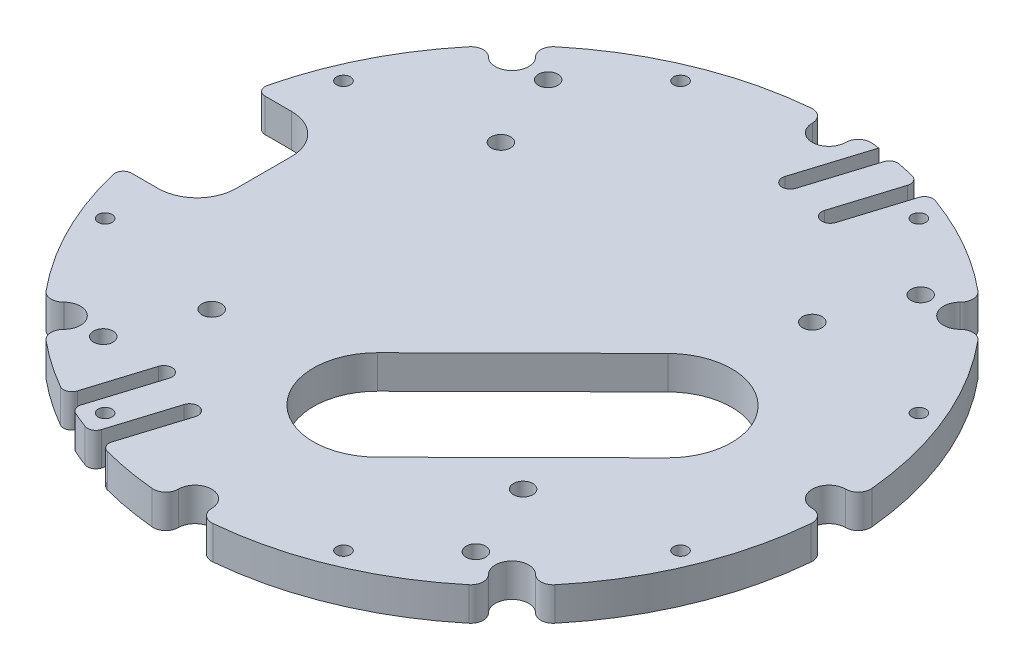
SolidWorks part; units mm, degrees
ref_plane "Ebene vorne" through (0, 0, 0) normal (0, 0, 1) x (1, 0, 0)
ref_plane "Ebene oben" through (0, 0, 0) normal (0, 1, 0) x (1, 0, 0)
ref_plane "Ebene rechts" through (0, 0, 0) normal (1, 0, 0) x (0, 0, -1)
sketch "Skizze1" plane through (0, 90.4001, 0) normal (0, 1, 0) x (1, 0, 0)
  line L0 (53.911, -33.2829) -> (49.3933, -47.7835)
  line L1 (24.4168, -148.1218) -> (28.8822, -133.7891)
  line L3 (-14.1957, -79.9654) -> (-7.542, -79.9654)
  line L4 (-0.542, -86.9654) -> (-0.542, -96.9654)
  line L5 (-7.542, -103.9654) -> (-14.1957, -103.9654)
  line L6 (-14.7061, -103.9654) -> (-7.542, -103.9654) construction
  line L7 (50.937, -32.8616) -> (46.3688, -47.5242)
  line L8 (10.5816, -51.9654) -> (77.5816, -131.9654) construction
  line L9 (27.3063, -149.0516) -> (31.7689, -134.728)
  line L10 (58.236, -49.7765) -> (62.6986, -35.4529)
  line L11 (77.5816, -51.9654) -> (10.5816, -51.9654) construction
  line L12 (23.359, -131.3458) -> (18.8412, -145.8464)
  line L13 (77.5816, -51.9654) -> (77.5816, -131.9654) construction
  line L14 (55.3269, -48.9096) -> (59.7923, -34.577)
  line L15 (77.5816, -131.9654) -> (10.5816, -131.9654) construction
  line L16 (20.7224, -129.8414) -> (16.1542, -144.504)
  line L18 (10.5816, -51.9654) -> (10.5816, -131.9654) construction
  line L19 (16.0816, -65.9654) -> (72.0816, -117.9654) construction
  line L20 (16.0816, -65.9654) -> (72.0816, -65.9654) construction
  line L21 (16.0816, -65.9654) -> (16.0816, -117.9654) construction
  line L22 (16.0816, -117.9654) -> (72.0816, -117.9654) construction
  line L23 (72.0816, -65.9654) -> (72.0816, -117.9654) construction
  line L24 (55.3269, -48.9096) -> (28.8822, -133.7891) construction
  line L27 (63.9849, -83.7988) -> (37.7607, -109.7988)
  line L28 (25.5156, -144.595) -> (19.7872, -142.8103) construction
  line L29 (80.1784, -100.1319) -> (53.9541, -126.1319)
  arc A0 (-5.9729, -58.8814) -> (-14.7061, -79.9654) centre (44.0816, -91.9654) ccw construction
  arc A1 (-5.9729, -58.8814) -> (-14.7061, -79.9654) centre (44.0816, -91.9654) ccw construction
  circle A2 centre (44.0816, -91.9654) radius 59.5
  arc A5 (-7.542, -79.9654) -> (-7.542, -103.9654) centre (44.0816, -91.9654) ccw construction
  arc A6 (-7.542, -79.9654) -> (-7.542, -103.9654) centre (44.0816, -91.9654) ccw construction
  arc A7 (-7.542, -79.9654) -> (-0.542, -86.9654) centre (-7.542, -86.9654) cw
  arc A8 (-0.542, -96.9654) -> (-7.542, -103.9654) centre (-7.542, -96.9654) cw
  circle A9 centre (22.6514, -40.2281) radius 1.25 construction
  circle A10 centre (22.6514, -40.2281) radius 1.25
  circle A11 centre (-7.6556, -70.5351) radius 1.25 construction
  circle A12 centre (-7.6556, -113.3956) radius 1.25 construction
  circle A13 centre (22.6514, -143.7026) radius 1.25 construction
  circle A14 centre (65.5119, -143.7026) radius 1.25 construction
  circle A15 centre (95.8189, -113.3956) radius 1.25 construction
  circle A16 centre (95.8189, -70.5351) radius 1.25 construction
  circle A17 centre (65.5119, -40.2281) radius 1.25 construction
  circle A18 centre (-7.6556, -70.5351) radius 1.25
  circle A19 centre (-7.6556, -113.3956) radius 1.25
  circle A20 centre (22.6514, -143.7026) radius 1.25
  circle A21 centre (65.5119, -143.7026) radius 1.25
  circle A22 centre (95.8189, -113.3956) radius 1.25
  circle A23 centre (95.8189, -70.5351) radius 1.25
  circle A24 centre (65.5119, -40.2281) radius 1.25
  arc A26 (49.3933, -47.7835) -> (46.3688, -47.5242) centre (44.0816, -91.9654) ccw
  arc A28 (55.3269, -48.9096) -> (49.3933, -47.7835) centre (44.0816, -91.9654) ccw construction
  arc A29 (31.7689, -134.728) -> (58.236, -49.7765) centre (44.0816, -91.9654) ccw construction
  arc A30 (58.236, -49.7765) -> (55.3269, -48.9096) centre (44.0816, -91.9654) ccw
  arc A31 (46.3688, -47.5242) -> (20.7224, -129.8414) centre (44.0816, -91.9654) ccw construction
  arc A32 (20.7224, -129.8414) -> (23.359, -131.3458) centre (44.0816, -91.9654) ccw
  arc A33 (23.359, -131.3458) -> (28.8822, -133.7891) centre (44.0816, -91.9654) ccw construction
  arc A34 (28.8822, -133.7891) -> (31.7689, -134.728) centre (44.0816, -91.9654) ccw
  circle A35 centre (77.5816, -51.9654) radius 1.75
  circle A36 centre (10.5816, -51.9654) radius 1.75
  circle A37 centre (10.5816, -131.9654) radius 1.75
  circle A38 centre (77.5816, -131.9654) radius 1.75
  circle A39 centre (16.0816, -65.9654) radius 1.75
  circle A40 centre (72.0816, -65.9654) radius 1.75
  circle A41 centre (72.0816, -117.9654) radius 1.75
  circle A42 centre (16.0816, -117.9654) radius 1.75
  arc A46 (80.1784, -100.1319) -> (63.9849, -83.7988) centre (72.0816, -91.9654) ccw
  arc A47 (37.7607, -109.7988) -> (53.9541, -126.1319) centre (45.8574, -117.9654) ccw
  point P5 (59.8996, -34.6182)
  point P17 (50.1571, -32.9645)
  point P18 (47.4097, -47.4938)
  point P78 (52.7585, -33.1014)
  point P83 (53.74, -33.2545)
  point P84 (17.0241, -144.9572)
  point P85 (0, 0)
  point P86 (15.4276, -144.3002)
  point P87 (50.8337, -32.5842)
  point P88 (53.9541, -33.2829)
  dimension "D1" = 119
  dimension "D2" = 6
  dimension "D3" = 12
  dimension "D4" = 89
  dimension "D6" = 3.5
  dimension "D11" = 23
  dimension "D5" = 10
  dimension "D7" = 67
  dimension "D8" = 80
  dimension "D9" = 56
  dimension "D10" = 52
extrude "Aufsatz-Linear austragen1" add sketch "Skizze1" along normal blind 6
sketch "Skizze2" plane through (0, 90.4001, 0) normal (0, 1, 0) x (1, 0, 0)
  line L11 (-7.542, -103.9654) -> (-14.1957, -103.9654)
  line L12 (16.1542, -144.504) -> (20.7224, -129.8414)
  line L13 (23.359, -131.3458) -> (18.8412, -145.8464)
  line L14 (24.4168, -148.1218) -> (28.8822, -133.7891)
  line L15 (31.7689, -134.728) -> (27.3063, -149.0516)
  line L16 (62.6986, -35.4529) -> (58.236, -49.7765)
  line L17 (55.3269, -48.9096) -> (59.7923, -34.577)
  line L18 (53.911, -33.2829) -> (49.3933, -47.7835)
  line L19 (46.3688, -47.5242) -> (50.937, -32.8616)
  line L20 (-14.1957, -79.9654) -> (-7.542, -79.9654)
  line L21 (-0.542, -86.9654) -> (-0.542, -96.9654)
  line L22 (-7.542, -103.9654) -> (-14.1957, -103.9654)
  line L23 (16.1542, -144.504) -> (20.7224, -129.8414)
  line L24 (23.359, -131.3458) -> (18.8412, -145.8464)
  line L25 (24.4168, -148.1218) -> (28.8822, -133.7891)
  line L26 (31.7689, -134.728) -> (27.3063, -149.0516)
  line L27 (62.6986, -35.4529) -> (58.236, -49.7765)
  line L28 (55.3269, -48.9096) -> (59.7923, -34.577)
  line L29 (53.911, -33.2829) -> (49.3933, -47.7835)
  line L30 (46.3688, -47.5242) -> (50.937, -32.8616)
  line L31 (-14.1957, -79.9654) -> (-7.542, -79.9654)
  line L32 (-0.542, -86.9654) -> (-0.542, -96.9654)
  circle A0 centre (44.0816, -91.9654) radius 43
  circle A1 centre (44.0816, -91.9654) radius 45
  arc A11 (-7.542, -103.9654) -> (-0.542, -96.9654) centre (-7.542, -96.9654) ccw
  arc A12 (-14.1957, -103.9654) -> (16.1542, -144.504) centre (44.0816, -91.9654) ccw
  arc A13 (20.7224, -129.8414) -> (23.359, -131.3458) centre (44.0816, -91.9654) ccw
  arc A14 (18.8412, -145.8464) -> (24.4168, -148.1218) centre (44.0816, -91.9654) ccw
  arc A15 (28.8822, -133.7891) -> (31.7689, -134.728) centre (44.0816, -91.9654) ccw
  arc A16 (27.3063, -149.0516) -> (62.6986, -35.4529) centre (44.0816, -91.9654) ccw
  arc A17 (58.236, -49.7765) -> (55.3269, -48.9096) centre (44.0816, -91.9654) ccw
  arc A18 (59.7923, -34.577) -> (53.911, -33.2829) centre (44.0816, -91.9654) ccw
  arc A19 (49.3933, -47.7835) -> (46.3688, -47.5242) centre (44.0816, -91.9654) ccw
  arc A20 (50.937, -32.8616) -> (-14.1957, -79.9654) centre (44.0816, -91.9654) ccw
  arc A21 (-0.542, -86.9654) -> (-7.542, -79.9654) centre (-7.542, -86.9654) ccw
  arc A22 (-7.542, -103.9654) -> (-0.542, -96.9654) centre (-7.542, -96.9654) ccw
  arc A23 (-14.1957, -103.9654) -> (16.1542, -144.504) centre (44.0816, -91.9654) ccw
  arc A24 (20.7224, -129.8414) -> (23.359, -131.3458) centre (44.0816, -91.9654) ccw
  arc A25 (18.8412, -145.8464) -> (24.4168, -148.1218) centre (44.0816, -91.9654) ccw
  arc A26 (28.8822, -133.7891) -> (31.7689, -134.728) centre (44.0816, -91.9654) ccw
  arc A27 (27.3063, -149.0516) -> (62.6986, -35.4529) centre (44.0816, -91.9654) ccw
  arc A28 (58.236, -49.7765) -> (55.3269, -48.9096) centre (44.0816, -91.9654) ccw
  arc A29 (59.7923, -34.577) -> (53.911, -33.2829) centre (44.0816, -91.9654) ccw
  arc A30 (49.3933, -47.7835) -> (46.3688, -47.5242) centre (44.0816, -91.9654) ccw
  arc A31 (50.937, -32.8616) -> (-14.1957, -79.9654) centre (44.0816, -91.9654) ccw construction
  arc A32 (-0.542, -86.9654) -> (-7.542, -79.9654) centre (-7.542, -86.9654) ccw
  dimension "D2" = 86
  dimension "D3" = 90
  dimension "D1" = 0
extrude "Schnitt-Linear austragen1" cut sketch "Skizze2" along normal blind 2 contours A1 A0
sketch "Skizze3" plane through (0, 96.4001, 0) normal (0, 1, 0) x (1, 0, 0)
  line L0 (1.6552, -53.7816) -> (5.8979, -49.539) construction
  circle A0 centre (44.0816, -34.9654) radius 1.25 construction
  circle A1 centre (84.3867, -51.6603) radius 1.25 construction
  circle A2 centre (101.0816, -91.9654) radius 1.25 construction
  circle A3 centre (84.3867, -132.2704) radius 1.25 construction
  circle A5 centre (3.7766, -132.2704) radius 1.25 construction
  circle A7 centre (3.7766, -51.6603) radius 1.25 construction
  circle A8 centre (44.0816, -34.9654) radius 1.25 construction
  circle A9 centre (84.3867, -51.6603) radius 1.25 construction
  circle A10 centre (101.0816, -91.9654) radius 1.25 construction
  circle A11 centre (84.3867, -132.2704) radius 1.25 construction
  circle A13 centre (3.7766, -132.2704) radius 1.25 construction
  circle A15 centre (3.7766, -51.6603) radius 1.25 construction
  arc A16 (50.937, -32.8616) -> (-14.1957, -79.9654) centre (44.0816, -91.9654) ccw construction
  arc A17 (6.0513, -46.2057) -> (5.8979, -49.539) centre (7.4945, -47.9423) ccw
  arc A18 (5.8979, -49.539) -> (1.6552, -53.7816) centre (3.7766, -51.6603) cw
  arc A19 (1.6552, -53.7816) -> (-1.678, -53.935) centre (0.0586, -55.3782) ccw
  circle A20 centre (44.0816, -91.9654) radius 59.5 construction
  arc A21 (49.547, -32.7169) -> (47.0816, -34.9654) centre (49.3396, -34.9654) ccw
  arc A22 (47.0816, -34.9654) -> (41.0816, -34.9654) centre (44.0816, -34.9654) cw
  arc A23 (41.0816, -34.9654) -> (38.6162, -32.7169) centre (38.8236, -34.9654) ccw
  arc A24 (89.8412, -53.935) -> (86.508, -53.7816) centre (88.1047, -55.3782) ccw
  arc A25 (86.508, -53.7816) -> (82.2654, -49.539) centre (84.3867, -51.6603) cw
  arc A26 (82.2654, -49.539) -> (82.112, -46.2057) centre (80.6688, -47.9423) ccw
  arc A27 (103.3301, -97.4308) -> (101.0816, -94.9654) centre (101.0816, -97.2234) ccw
  arc A28 (101.0816, -94.9654) -> (101.0816, -88.9654) centre (101.0816, -91.9654) cw
  arc A29 (101.0816, -88.9654) -> (103.3301, -86.5) centre (101.0816, -86.7074) ccw
  arc A30 (82.112, -137.725) -> (82.2654, -134.3918) centre (80.6688, -135.9884) ccw
  arc A31 (82.2654, -134.3918) -> (86.508, -130.1491) centre (84.3867, -132.2704) cw
  arc A32 (86.508, -130.1491) -> (89.8412, -129.9957) centre (88.1047, -128.5525) ccw
  arc A33 (38.6162, -151.2138) -> (41.0816, -148.9654) centre (38.8236, -148.9654) ccw
  arc A34 (41.0816, -148.9654) -> (47.0816, -148.9654) centre (44.0816, -148.9654) cw
  arc A35 (47.0816, -148.9654) -> (49.547, -151.2138) centre (49.3396, -148.9654) ccw
  arc A36 (-1.678, -129.9957) -> (1.6552, -130.1491) centre (0.0586, -128.5525) ccw
  arc A37 (1.6552, -130.1491) -> (5.8979, -134.3918) centre (3.7766, -132.2704) cw
  arc A38 (5.8979, -134.3918) -> (6.0513, -137.725) centre (7.4945, -135.9884) ccw
  arc A39 (-15.1668, -86.5) -> (-12.9184, -88.9654) centre (-12.9184, -86.7074) ccw construction
  arc A40 (-12.9184, -88.9654) -> (-12.9184, -94.9654) centre (-12.9184, -91.9654) cw construction
  arc A44 (-12.9184, -94.9654) -> (-15.1668, -97.4308) centre (-12.9184, -97.2234) ccw construction
  circle A45 centre (44.0816, -91.9654) radius 75
  point P82 (44.0816, -91.9654)
  arc M30 (-0.542, -96.9654) -> (-7.542, -103.9654) centre (-7.542, -96.9654) cw
  line M31 (-7.542, -103.9654) -> (-14.1957, -103.9654)
  arc M32 (-14.1957, -103.9654) -> (16.1542, -144.504) centre (44.0816, -91.9654) ccw
  line M33 (16.1542, -144.504) -> (20.7224, -129.8414)
  arc M34 (20.7224, -129.8414) -> (23.359, -131.3458) centre (44.0816, -91.9654) ccw
  line M35 (23.359, -131.3458) -> (18.8412, -145.8464)
  arc M36 (18.8412, -145.8464) -> (24.4168, -148.1218) centre (44.0816, -91.9654) ccw
  line M37 (24.4168, -148.1218) -> (28.8822, -133.7891)
  arc M38 (28.8822, -133.7891) -> (31.7689, -134.728) centre (44.0816, -91.9654) ccw
  line M39 (31.7689, -134.728) -> (27.3063, -149.0516)
  arc M40 (27.3063, -149.0516) -> (62.6986, -35.4529) centre (44.0816, -91.9654) ccw
  line M41 (62.6986, -35.4529) -> (58.236, -49.7765)
  arc M42 (58.236, -49.7765) -> (55.3269, -48.9096) centre (44.0816, -91.9654) ccw
  line M43 (55.3269, -48.9096) -> (59.7923, -34.577)
  arc M44 (59.7923, -34.577) -> (53.911, -33.2829) centre (44.0816, -91.9654) ccw
  line M45 (53.911, -33.2829) -> (49.3933, -47.7835)
  arc M46 (49.3933, -47.7835) -> (46.3688, -47.5242) centre (44.0816, -91.9654) ccw
  line M47 (46.3688, -47.5242) -> (50.937, -32.8616)
  arc M48 (50.937, -32.8616) -> (-14.1957, -79.9654) centre (44.0816, -91.9654) ccw
  line M49 (-14.1957, -79.9654) -> (-7.542, -79.9654)
  arc M50 (-7.542, -79.9654) -> (-0.542, -86.9654) centre (-7.542, -86.9654) cw
  line M51 (-0.542, -86.9654) -> (-0.542, -96.9654)
  dimension "D1" = 3
  dimension "D3" = 150
  dimension "D2" = 8
extrude "Schnitt-Linear austragen2" cut sketch "Skizze3" against normal through all contours A37 A38 A33 A34 A35 A30 A31 A32 A27 A28 A29 A24 A25 A26 A21 A22 A23 A17 A18 A19 A36 M32 M33 M34 M35 M36 M37 M38 M39 M40 M41 M42 M43 M44 M45 M46 M47 M48 M49 M50 M51 M30 M31 | A45
fillet "Verrundung3" radius 1.5 15 edges at (27.3063, 93.4001, 149.0516) (24.4168, 93.4001, 148.1218) (18.8412, 93.4001, 145.8464) (16.1542, 93.4001, 144.504) (20.7224, 94.4001, 129.8414) (28.8822, 94.4001, 133.7891) (31.7689, 94.4001, 134.728) (23.359, 94.4001, 131.3458) (55.3269, 94.4001, 48.9096) (46.3688, 94.4001, 47.5242) (53.911, 93.4001, 33.2829) (49.3933, 94.4001, 47.7835) (59.7923, 93.4001, 34.577) (62.6986, 93.4001, 35.4529) (58.236, 94.4001, 49.7765)
fillet "Verrundung4" radius 1.5 2 edges at (-14.1957, 93.4001, 79.9654) (-14.1957, 93.4001, 103.9654)
